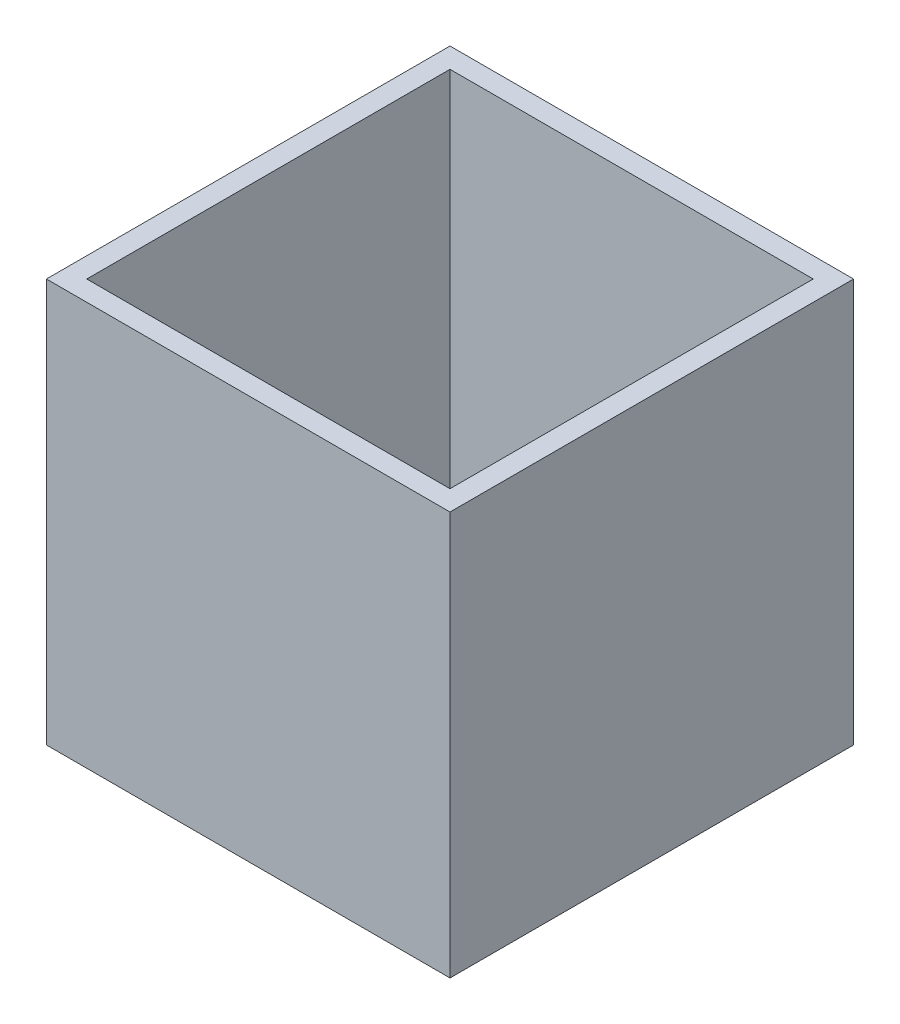
SolidWorks part; units mm, degrees
ref_plane "Front Plane" through (0, 0, 0) normal (0, 0, 1) x (1, 0, 0)
ref_plane "Top Plane" through (0, 0, 0) normal (0, 1, 0) x (1, 0, 0)
ref_plane "Right Plane" through (0, 0, 0) normal (1, 0, 0) x (0, 0, -1)
sketch "Sketch1" plane through (0, 0, 0) normal (0, 1, 0) x (1, 0, 0)
  line L1 (0, 0) -> (-20, 0)
  line L2 (0, 0) -> (0, 20)
  line L3 (0, 20) -> (-20, 20)
  line L4 (-20, 0) -> (-20, 20)
  dimension "D1" = 20
  dimension "D2" = 20
extrude "Boss-Extrude1" add sketch "Sketch1" along normal blind 20
shell "Shell1" thickness 1 removed face at (-10, 20, -10)
sketch "Sketch2" plane through (0, 0, 0) normal (0, -1, 0) x (1, 0, 0)
  circle A1 centre (-14.4534, -15.0144) radius 0.5
  circle A2 centre (-10.0703, -9.1833) radius 3
  dimension "D2" = 1
  dimension "D3" = 6
extrude "Cut-Extrude1" cut sketch "Sketch2" against normal through all
sketch "Sketch3" plane through (0, 0, 0) normal (0, -1, 0) x (-1, 0, 0)
  line L2 (1.9017, 4.3214) -> (5.9638, 4.3214)
  line L3 (1.9017, 4.3214) -> (1.9017, 4.9214)
  line L4 (1.9017, 4.9214) -> (5.9638, 4.9214)
  line L5 (5.9638, 4.3214) -> (5.9638, 4.9214)
  dimension "D1" = 0.6
extrude "Cut-Extrude2" cut sketch "Sketch3" against normal blind 10
